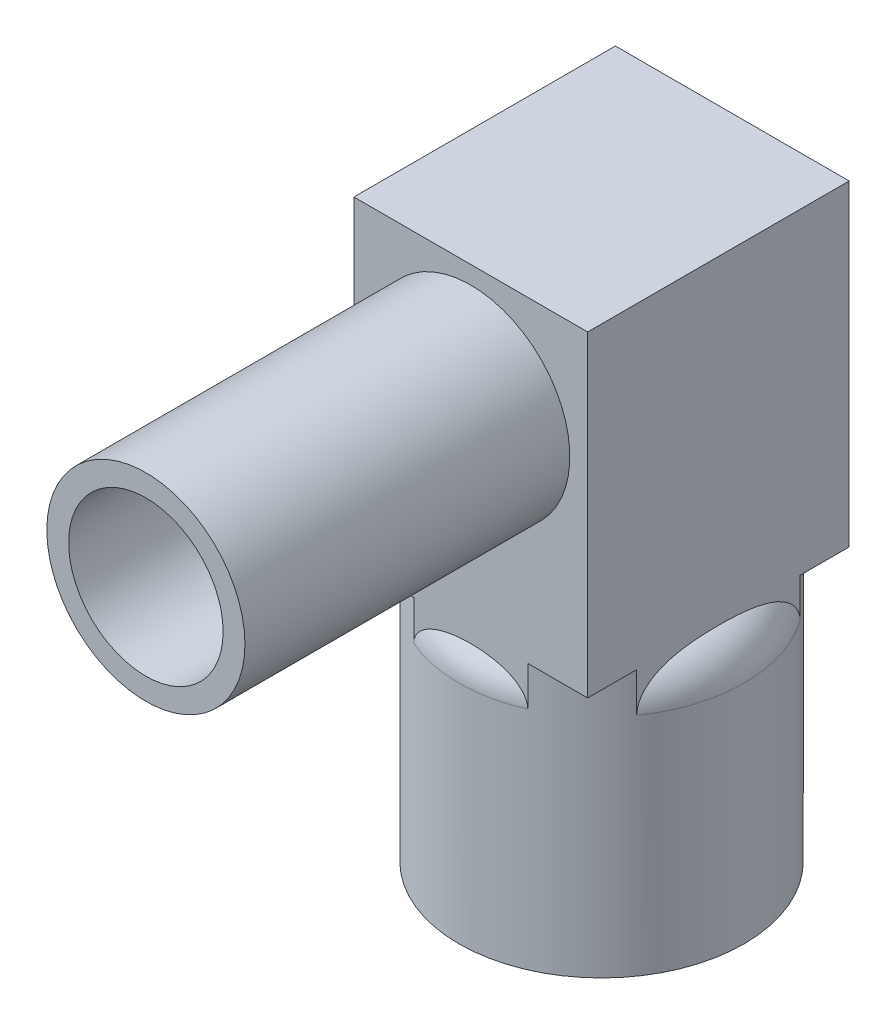
SolidWorks part; units mm, degrees
ref_plane "Front Plane" through (0, 0, 0) normal (0, 0, 1) x (1, 0, 0)
ref_plane "Top Plane" through (0, 0, 0) normal (0, 1, 0) x (1, 0, 0)
ref_plane "Right Plane" through (0, 0, 0) normal (1, 0, 0) x (0, 0, -1)
sketch "Sketch1" plane through (0, 0, 0) normal (0, 1, 0) x (1, 0, 0)
  circle A0 centre (-13.8446, 2.2538) radius 9.144
  dimension "D1" = 18.288
extrude "Boss-Extrude1" add sketch "Sketch1" along normal blind 17.018
sketch "Sketch2" plane through (0, 17.018, 0) normal (0, 1, 0) x (1, 0, 0)
  line L1 (-21.3376, -6.1282) -> (-6.3516, -6.1282)
  line L2 (-21.3376, -6.1282) -> (-21.3376, 10.6358)
  line L3 (-21.3376, 10.6358) -> (-6.3516, 10.6358)
  line L4 (-6.3516, -6.1282) -> (-6.3516, 10.6358)
  line L5 (-21.3376, -6.1282) -> (-6.3516, 10.6358) construction
  line L6 (-21.3376, 10.6358) -> (-6.3516, -6.1282) construction
  point P0 (-13.8446, 2.2538)
  dimension "D1" = 14.986
  dimension "D2" = 16.764
extrude "Boss-Extrude2" add sketch "Sketch2" along normal blind 20.32
sketch "Sketch3" plane through (0, 0, 6.1282) normal (0, 0, 1) x (1, 0, 0)
  line L0 (-21.3376, 22.352) -> (-6.3516, 22.352) construction
  line L1 (-21.3376, 37.338) -> (-21.3376, 17.018) construction
  line L2 (-6.3516, 37.338) -> (-6.3516, 17.018) construction
  line L3 (-21.3376, 37.338) -> (-6.3516, 37.338) construction
  line L4 (-13.8446, 37.338) -> (-13.8446, 22.352) construction
  line L5 (-21.3376, 29.845) -> (-6.3516, 29.845) construction
  circle A0 centre (-13.8446, 29.845) radius 6.35
  dimension "D3" = 12.7
  dimension "D1" = 14.986
  dimension "D2" = 7.493
extrude "Boss-Extrude3" add sketch "Sketch3" along normal blind 20.828
sketch "Sketch5" plane through (0, 0, 26.9562) normal (0, 0, 1) x (1, 0, 0)
  circle A0 centre (-13.8446, 29.845) radius 4.953
  dimension "D1" = 9.906
extrude "Cut-Extrude1" cut sketch "Sketch5" against normal blind 25.4
sketch "Sketch6" plane through (0, 0, 0) normal (0, -1, 0) x (1, 0, 0)
  circle A0 centre (-13.9479, -2.5167) radius 6.985
  dimension "D1" = 13.97
extrude "Cut-Extrude2" cut sketch "Sketch6" against normal blind 35.56
fillet "Fillet3" radius 2.54 4 edges at (-22.9886, 17.018, -2.2538) (-13.8446, 17.018, 6.8902) (-13.8446, 17.018, -11.3978) (-4.7006, 17.018, -2.2538)
